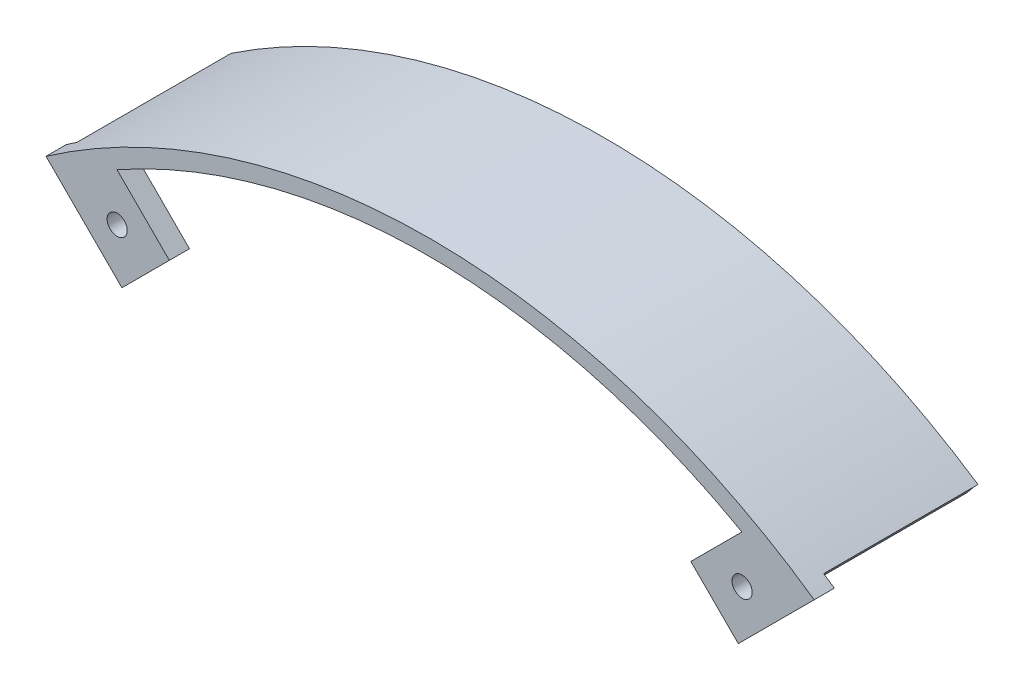
SolidWorks part; units mm, degrees
material "ABS"
ref_plane "Alzado" through (0, 0, 0) normal (0, 0, 1) x (1, 0, 0)
ref_plane "Planta" through (0, 0, 0) normal (0, 1, 0) x (1, 0, 0)
ref_plane "Vista lateral" through (0, 0, 0) normal (1, 0, 0) x (0, 0, -1)
sketch "Croquis1" plane through (0, 0, 0) normal (0, 0, 1) x (1, 0, 0)
  circle A0 centre (0, 0) radius 100
  dimension "D1" = 200
extrude "Saliente-Extruir1" add sketch "Croquis1" along normal blind 3
sketch "Croquis3" plane through (0, 0, 3) normal (0, 0, 1) x (1, 0, 0)
  line L0 (0, 0) -> (190, 0) construction
  circle A0 centre (190, 0) radius 110
  dimension "D1" = 220
  dimension "D2" = 190
extrude "Cortar-Extruir1" cut sketch "Croquis3" against normal blind 3
fillet "Redondeo1" radius 10 2 edges at (89.4737, -44.6594, 1.5) (89.4737, 44.6594, 1.5)
sketch "Croquis5" plane through (0, 0, 3) normal (0, 0, 1) x (1, 0, 0)
  line L0 (0, -100) -> (0, 100) construction
  line L1 (-100, 0) -> (80, 0) construction
  line L2 (0, 0) -> (-70.7107, -70.7107) construction
  line L3 (-70.7107, -70.7107) -> (70.7107, 70.7107) construction
  line L4 (0, 0) -> (-70.7107, 70.7107) construction
  line L5 (-70.7107, 70.7107) -> (70.7107, -70.7107) construction
  line L6 (-70.7107, -70.7107) -> (-58.3363, -83.085) construction
  line L9 (-58.3363, -83.085) -> (-83.085, -58.3363)
  line L11 (-83.085, -58.3363) -> (-65.4074, -40.6586)
  line L12 (-65.4074, -40.6586) -> (-40.6586, -65.4074)
  line L13 (-40.6586, -65.4074) -> (-58.3363, -83.085)
  line L14 (-70.7107, 70.7107) -> (-83.085, 58.3363) construction
  line L15 (-83.085, 58.3363) -> (-100, 0) construction
  line L17 (-83.085, 58.3363) -> (-58.3363, 83.085)
  line L18 (-58.3363, 83.085) -> (-40.6586, 65.4074)
  line L19 (-40.6586, 65.4074) -> (-65.4074, 40.6586)
  line L20 (-65.4074, 40.6586) -> (-83.085, 58.3363)
  line L22 (70.7107, -70.7107) -> (58.3363, -83.085) construction
  line L23 (58.3363, -83.085) -> (0, -100) construction
  line L24 (58.3363, -83.085) -> (83.085, -58.3363)
  line L25 (83.085, -58.3363) -> (65.4074, -40.6586)
  line L26 (65.4074, -40.6586) -> (40.6586, -65.4074)
  line L27 (40.6586, -65.4074) -> (58.3363, -83.085)
  line L28 (70.7107, 70.7107) -> (58.3363, 83.085) construction
  line L29 (58.3363, 83.085) -> (0, 100) construction
  line L30 (58.3363, 83.085) -> (83.085, 58.3363)
  line L31 (83.085, 58.3363) -> (65.4074, 40.6586)
  line L32 (65.4074, 40.6586) -> (40.6586, 65.4074)
  line L33 (40.6586, 65.4074) -> (58.3363, 83.085)
  arc A0 (87.1345, 49.0671) -> (87.1345, -49.0671) centre (0, 0) ccw construction
  arc A1 (87.7193, 40.4803) -> (87.7193, -40.4803) centre (190, 0) ccw construction
  point P36 (0, 0)
  dimension "D2" = 17.5
  dimension "D3" = 25
  dimension "D4" = 35
  dimension "D5" = 25
  dimension "D6" = 35
  dimension "D8" = 25
  dimension "D9" = 17.5
  dimension "D7" = 35
  dimension "D10" = 90
  dimension "D11" = 17.5
  dimension "D12" = 17.5
  dimension "D13" = 35
  dimension "D14" = 25
  dimension "D15" = 134.3503
  dimension "D16" = 100
extrude "Cortar-Extruir6" cut sketch "Croquis5" against normal blind 10
sketch "Croquis12" plane through (0, 0, 3) normal (0, 0, 1) x (1, 0, 0)
  line L0 (-53.033, -53.033) -> (-39.9421, -50.0116) construction
  line L1 (-40.6586, -65.4074) -> (-65.4074, -40.6586) construction
  line L2 (-39.9421, -50.0116) -> (-36.8049, -63.6043) construction
  line L3 (-36.8049, -63.6043) -> (-63.6043, -36.8049) construction
  line L4 (-63.6043, -36.8049) -> (-47.6661, -20.8667) construction
  line L6 (53.033, -53.033) -> (-53.033, 53.033) construction
  line L7 (65.4074, -40.6586) -> (40.6586, -65.4074) construction
  line L8 (-65.4074, 40.6586) -> (-40.6586, 65.4074) construction
  line L9 (36.8049, 63.6043) -> (20.8667, 47.6661) construction
  line L10 (63.6043, 36.8049) -> (36.8049, 63.6043) construction
  line L11 (50.0116, 39.9421) -> (63.6043, 36.8049) construction
  line L12 (53.033, 53.033) -> (50.0116, 39.9421) construction
  line L14 (53.033, -53.033) -> (50.2046, -50.2046) construction
  line L15 (50.2046, -50.2046) -> (36.8049, -63.6043) construction
  line L16 (36.8049, -63.6043) -> (63.6043, -36.8049) construction
  line L17 (63.6043, -36.8049) -> (47.6661, -20.8667) construction
  line L19 (-53.033, -53.033) -> (53.033, 53.033) construction
  line L20 (-36.8049, 63.6043) -> (-20.8667, 47.6661) construction
  line L21 (-63.6043, 36.8049) -> (-36.8049, 63.6043) construction
  line L22 (-50.2046, 50.2046) -> (-63.6043, 36.8049) construction
  line L23 (-53.033, 53.033) -> (-50.2046, 50.2046) construction
  circle A0 centre (-63.6043, -36.8049) radius 1.5
  circle A1 centre (-36.8049, -63.6043) radius 1.5
  circle A2 centre (-47.6661, -20.8667) radius 1.5
  circle A3 centre (-20.8667, -47.6661) radius 1.5
  circle A5 centre (47.6661, 20.8667) radius 1.5
  circle A6 centre (20.8667, 47.6661) radius 1.5
  circle A7 centre (63.6043, 36.8049) radius 1.5
  circle A8 centre (36.8049, 63.6043) radius 1.5
  circle A10 centre (20.8667, -47.6661) radius 1.5
  circle A11 centre (47.6661, -20.8667) radius 1.5
  circle A12 centre (63.6043, -36.8049) radius 1.5
  circle A13 centre (36.8049, -63.6043) radius 1.5
  circle A15 centre (-63.6043, 36.8049) radius 1.5
  circle A16 centre (-36.8049, 63.6043) radius 1.5
  circle A17 centre (-20.8667, 47.6661) radius 1.5
  circle A18 centre (-47.6661, 20.8667) radius 1.5
  dimension "D2" = 3
  dimension "D3" = 3
  dimension "D4" = 4
  dimension "D5" = 4
  dimension "D6" = 3
  dimension "D7" = 3
  dimension "D8" = 37.9
  dimension "D9" = 22.54
  dimension "D10" = 22.54
  dimension "D11" = 37.9
  dimension "D12" = 18.95
  dimension "D13" = 18.95
  dimension "D14" = 3
  dimension "D15" = 3
  dimension "D16" = 3
  dimension "D17" = 3
  dimension "D18" = 37.9
  dimension "D19" = 22.54
  dimension "D20" = 22.54
  dimension "D21" = 37.9
  dimension "D22" = 4
  dimension "D1" = 13.95
extrude "Cortar-Extruir7" cut sketch "Croquis12" against normal through all
sketch "Croquis9" plane through (0, 0, 3) normal (0, 0, 1) x (1, 0, 0)
  line L0 (0, 0) -> (-100, 0) construction
  line L5 (0, 100) -> (0, -100) construction
  line L6 (38.9591, 4) -> (43.4591, 4)
  line L7 (38.9591, 4) -> (38.9591, -4)
  line L8 (38.9591, -4) -> (43.4591, -4)
  line L9 (43.4591, 4) -> (43.4591, -4)
  line L10 (-4, -52) -> (4, -52)
  line L11 (-58.1901, 4) -> (-62.6901, 4)
  line L12 (-58.1901, 4) -> (-58.1901, -4)
  line L13 (-58.1901, -4) -> (-62.6901, -4)
  line L14 (-62.6901, 4) -> (-62.6901, -4)
  line L15 (-4, 56.5) -> (4, 56.5)
  line L16 (-4, 56.5) -> (-4, 52)
  line L17 (-4, 52) -> (4, 52)
  line L18 (4, 56.5) -> (4, 52)
  line L19 (4, -56.5) -> (4, -52)
  line L20 (-4, -56.5) -> (4, -56.5)
  line L21 (-4, -56.5) -> (-4, -52)
  line L22 (0, 0) -> (80, 0) construction
  line L24 (-58.2511, -4) -> (-58.2738, -4) construction
  circle A0 centre (71.9, -4) radius 1.5
  circle A1 centre (35.9591, 4) radius 1.5
  circle A4 centre (71.9591, 4) radius 1.5
  circle A5 centre (35.9, -4) radius 1.5
  arc A6 (-81.9939, 57.2451) -> (-81.9939, -57.2451) centre (0, 0) ccw construction
  arc A7 (87.7193, 40.4803) -> (87.7193, -40.4803) centre (190, 0) ccw construction
  circle A8 centre (-91.1901, 4) radius 1.5
  circle A9 centre (-91.1901, -4) radius 1.5
  circle A10 centre (-55.1901, 4) radius 1.5
  circle A11 centre (-55.1901, -4) radius 1.5
  circle A12 centre (-4, 85) radius 1.5
  circle A13 centre (4, 85) radius 1.5
  circle A14 centre (-4, 49) radius 1.5
  circle A15 centre (4, 49) radius 1.5
  circle A20 centre (-4, -49) radius 1.5
  circle A21 centre (4, -49) radius 1.5
  circle A22 centre (4, -85) radius 1.5
  circle A23 centre (-4, -85) radius 1.5
  arc A24 (87.1345, 49.0671) -> (81.9939, 57.2451) centre (0, 0) ccw construction
  arc A25 (57.2451, 81.9939) -> (-57.2451, 81.9939) centre (0, 0) ccw construction
  dimension "D6" = 35.9
  dimension "D7" = 3
  dimension "D8" = 36
  dimension "D9" = 36
  dimension "D10" = 3
  dimension "D11" = 3
  dimension "D12" = 4
  dimension "D13" = 4
  dimension "D14" = 3
  dimension "D15" = 3
  dimension "D16" = 3
  dimension "D21" = 4
  dimension "D22" = 4
  dimension "D23" = 3
  dimension "D24" = 3
  dimension "D25" = 4
  dimension "D26" = 4
  dimension "D27" = 36
  dimension "D28" = 36
  dimension "D29" = 91.1901
  dimension "D30" = 91.1901
  dimension "D35" = 3
  dimension "D36" = 3
  dimension "D37" = 8
  dimension "D38" = 4
  dimension "D39" = 3
  dimension "D40" = 3
  dimension "D41" = 8
  dimension "D42" = 36
  dimension "D43" = 36
  dimension "D44" = 36
  dimension "D45" = 4
  dimension "D46" = 4
  dimension "D51" = 4
  dimension "D52" = 4
  dimension "D53" = 36.1809
  dimension "D55" = 36
  dimension "D56" = 49
  dimension "D57" = 49
  dimension "D58" = 3
  dimension "D59" = 3
  dimension "D60" = 3
  dimension "D61" = 3
  dimension "D62" = 4.5
  dimension "D32" = 8
  dimension "D64" = 0
  dimension "D69" = 8
  dimension "D70" = 4
  dimension "D71" = 85.0941
  dimension "D72" = 85.0941
  dimension "D17" = 4.5
  dimension "D18" = 8
  dimension "D19" = 3
  dimension "D20" = 0
  dimension "D31" = 3.061
  dimension "D33" = 3
  dimension "D34" = 0
  dimension "D47" = 8
  dimension "D48" = 4.5
  dimension "D49" = 0
  dimension "D50" = 3
  dimension "D54" = 4
  dimension "D63" = 0
  dimension "D65" = 3
  dimension "D66" = 4.5
  dimension "D67" = 8
  dimension "D68" = 3
extrude "Cortar-Extruir5" cut sketch "Croquis9" against normal blind 10
sketch "Croquis13" plane through (0, 0, 3) normal (0, 0, 1) x (1, 0, 0)
  line L0 (-57.2451, 81.9939) -> (-53.7096, 78.4583) construction
  line L1 (-40.6586, 65.4074) -> (-57.2451, 81.9939) construction
  line L2 (57.2451, 81.9939) -> (53.4895, 78.2383) construction
  line L3 (57.2451, 81.9939) -> (40.6586, 65.4074) construction
  line L4 (0, 100) -> (0, 95) construction
  line L5 (-53.7096, 78.4583) -> (-40.6586, 65.4074)
  line L6 (-40.6586, 65.4074) -> (-65.4074, 40.6586)
  line L7 (-65.4074, 40.6586) -> (-81.9939, 57.2451)
  line L8 (-81.9939, -57.2451) -> (-65.4074, -40.6586)
  line L9 (-65.4074, -40.6586) -> (-40.6586, -65.4074)
  line L10 (-40.6586, -65.4074) -> (-57.2451, -81.9939)
  line L12 (81.9939, -57.2451) -> (65.4074, -40.6586)
  line L13 (65.4074, -40.6586) -> (40.6586, -65.4074)
  line L14 (40.6586, -65.4074) -> (57.2451, -81.9939)
  line L15 (53.4895, 78.2383) -> (40.6586, 65.4074)
  line L16 (40.6586, 65.4074) -> (65.4074, 40.6586)
  line L17 (65.4074, 40.6586) -> (81.9939, 57.2451)
  arc A0 (57.2451, 81.9939) -> (-57.2451, 81.9939) centre (0, 0) ccw construction
  arc A1 (-53.7096, 78.4583) -> (53.4895, 78.2383) centre (-0.2711, -0.0867) cw
  arc A2 (-81.9939, 57.2451) -> (-81.9939, -57.2451) centre (0, 0) ccw
  arc A3 (-57.2451, -81.9939) -> (57.2451, -81.9939) centre (0, 0) ccw
  arc A4 (87.7193, -40.4803) -> (87.7193, 40.4803) centre (190, 0) cw
  arc A7 (81.9939, -57.2451) -> (87.7193, -40.4803) centre (81.3824, -47.6762) ccw
  arc A8 (81.9939, 57.2451) -> (87.7193, 40.4803) centre (84.8566, 48.8627) cw
  dimension "D2" = 95
  dimension "D3" = 100
  dimension "D4" = 110
  dimension "D5" = 100
  dimension "D6" = 0.2846
  dimension "D7" = 17.753
  dimension "D1" = 5
extrude "Cortar-Extruir9" cut sketch "Croquis13" against normal through all
sketch "Croquis14" plane through (0, 0, 0) normal (0, 0, -1) x (-1, 0, 0)
  line L1 (45.9314, 70.6802) -> (38.8604, 77.7512)
  line L4 (-45.9314, 70.6802) -> (-38.8604, 77.7512)
  line L6 (45.9314, 70.6802) -> (53.7096, 78.4583)
  line L7 (38.8604, 77.7512) -> (44.8915, 83.7824)
  line L8 (-45.9314, 70.6802) -> (-53.4895, 78.2383)
  line L9 (-38.8604, 77.7512) -> (-44.7026, 83.5935)
  arc A3 (53.7096, 78.4583) -> (-53.4895, 78.2383) centre (0.2711, -0.0867) ccw construction
  arc A4 (53.7096, 78.4583) -> (44.8915, 83.7824) centre (0.2711, -0.0867) ccw
  arc A5 (-53.4895, 78.2383) -> (-44.7026, 83.5935) centre (0.2711, -0.0867) cw
  dimension "D4" = 95
  dimension "D8" = 95
  dimension "D1" = 10.6888
  dimension "D2" = 10
  dimension "D3" = 8.2622
  dimension "D5" = 8.5293
  dimension "D6" = 10
  dimension "D7" = 11
  dimension "D9" = 82.7098
extrude "Saliente-Extruir3" add sketch "Croquis14" against normal blind 3
sketch "Croquis15" plane through (0, 0, 3) normal (0, 0, 1) x (1, 0, 0)
  line L0 (57.2451, 81.9939) -> (45.9314, 70.6802)
  line L1 (45.9314, 70.6802) -> (38.8604, 77.7512)
  line L2 (38.8604, 77.7512) -> (44.7026, 83.5935)
  line L3 (-44.8915, 83.7824) -> (-38.8604, 77.7512)
  line L4 (-38.8604, 77.7512) -> (-45.9314, 70.6802)
  line L5 (-45.9314, 70.6802) -> (-57.2451, 81.9939)
  line L8 (0, 100) -> (0, 97.5) construction
  arc A0 (57.2451, 81.9939) -> (-57.2451, 81.9939) centre (0, 0) ccw
  arc A1 (44.7026, 83.5935) -> (-44.8915, 83.7824) centre (-0.2711, -0.0867) ccw
  dimension "D1" = 100
  dimension "D2" = 95
  dimension "D3" = 2.5
extrude "Saliente-Extruir4" add sketch "Croquis15" along normal blind 23
sketch "Croquis16" plane through (0, 0, 0) normal (0, 0, -1) x (-1, 0, 0)
  line L0 (-44.7026, 83.5935) -> (-46.4704, 85.3612)
  line L1 (44.8915, 83.7824) -> (46.6592, 85.5501)
  arc A0 (-46.4704, 85.3612) -> (46.6592, 85.5501) centre (0.2624, 2.6506) cw
  arc A1 (-44.7026, 83.5935) -> (44.8915, 83.7824) centre (0.2711, -0.0867) cw
  arc A2 (57.2451, 81.9939) -> (-57.2451, 81.9939) centre (0, 0) ccw construction
  dimension "D3" = 95
  dimension "D4" = 95
  dimension "D5" = 2.6635
  dimension "D1" = 2.5
  dimension "D2" = 2.5
extrude "Cortar-Extruir10" cut sketch "Croquis16" against normal through all
sketch "Croquis17" plane through (0, 0, 0) normal (0, 0, -1) x (-1, 0, 0)
  line L0 (-45.9314, 70.6802) -> (-55.4774, 80.2261)
  line L1 (-57.2451, 81.9939) -> (-45.9314, 70.6802) construction
  line L2 (-45.9314, 70.6802) -> (-38.8604, 77.7512)
  line L3 (-38.8604, 77.7512) -> (-46.4704, 85.3612)
  line L4 (46.6592, 85.5501) -> (38.8604, 77.7512)
  line L5 (38.8604, 77.7512) -> (45.9314, 70.6802)
  line L6 (57.2451, 81.9939) -> (55.4774, 80.2261) construction
  line L7 (45.9314, 70.6802) -> (57.2451, 81.9939) construction
  line L8 (55.4774, 80.2261) -> (45.9314, 70.6802)
  line L9 (-46.4704, 85.3612) -> (-55.4774, 80.2261)
  line L10 (55.4774, 80.2261) -> (46.6592, 85.5501)
  dimension "D1" = 13.5
  dimension "D2" = 13.5
extrude "Cortar-Extruir11" cut sketch "Croquis17" against normal blind 23
sketch "Croquis20" plane through (0, 0, 0) normal (0, 0, -1) x (-1, 0, 0)
  line L0 (57.2451, 81.9939) -> (55.4774, 80.2261)
  line L1 (55.4774, 80.2261) -> (46.6592, 85.5501) construction
  line L2 (55.5571, 83.0598) -> (53.7616, 81.262)
  line L3 (-57.2451, 81.9939) -> (-55.4774, 80.2261)
  line L4 (-46.4704, 85.3612) -> (-55.4774, 80.2261) construction
  line L5 (-53.927, 81.11) -> (-55.5535, 83.0598)
  arc A0 (55.4774, 80.2261) -> (53.7616, 81.262) centre (55.1321, 81.5932) cw
  arc A1 (57.2451, 81.9939) -> (55.5571, 83.0598) centre (55.8682, 81.6828) ccw
  arc A2 (57.2451, 81.9939) -> (-57.2451, 81.9939) centre (0, 0) ccw construction
  arc A3 (-55.4774, 80.2261) -> (-53.927, 81.11) centre (-55.1441, 81.4432) ccw
  arc A4 (-57.2451, 81.9939) -> (-55.5535, 83.0598) centre (-55.8663, 81.681) cw
  dimension "D1" = 1.4117
  dimension "D2" = 1.41
  dimension "D4" = 0.736
  dimension "D5" = 98.9613
  dimension "D7" = 0.8923
  dimension "D8" = 98.9588
  dimension "D9" = 0.7222
  dimension "D10" = 1.2619
  dimension "D3" = 2.5409
  dimension "D6" = 2.5391
extrude "Cortar-Extruir14" cut sketch "Croquis20" against normal blind 23
sketch "Croquis21" plane through (0, 0, 23) normal (0, 0, -1) x (-1, 0, 0)
  line L0 (-57.1062, 81.8549) -> (-50.0351, 74.7839) construction
  line L1 (-57.2451, 81.9939) -> (-45.9314, 70.6802) construction
  line L2 (-50.0351, 74.7839) -> (-46.4996, 78.3194) construction
  line L3 (-45.9314, 70.6802) -> (-38.8604, 77.7512) construction
  line L4 (-38.8604, 77.7512) -> (-46.4704, 85.3612) construction
  line L5 (57.2451, 81.9939) -> (50.1741, 74.9228) construction
  line L6 (45.9314, 70.6802) -> (57.2451, 81.9939) construction
  line L7 (50.1741, 74.9228) -> (46.6385, 78.4583) construction
  line L8 (38.8604, 77.7512) -> (45.9314, 70.6802) construction
  line L9 (46.6592, 85.5501) -> (38.8604, 77.7512) construction
  circle A0 centre (-46.4996, 78.3194) radius 1.5
  circle A1 centre (46.6385, 78.4583) radius 1.5
  dimension "D1" = 3
  dimension "D2" = 5.8035
  dimension "D3" = 5
  dimension "D4" = 3
  dimension "D5" = 6
  dimension "D6" = 5
extrude "Cortar-Extruir15" cut sketch "Croquis21" against normal through all
